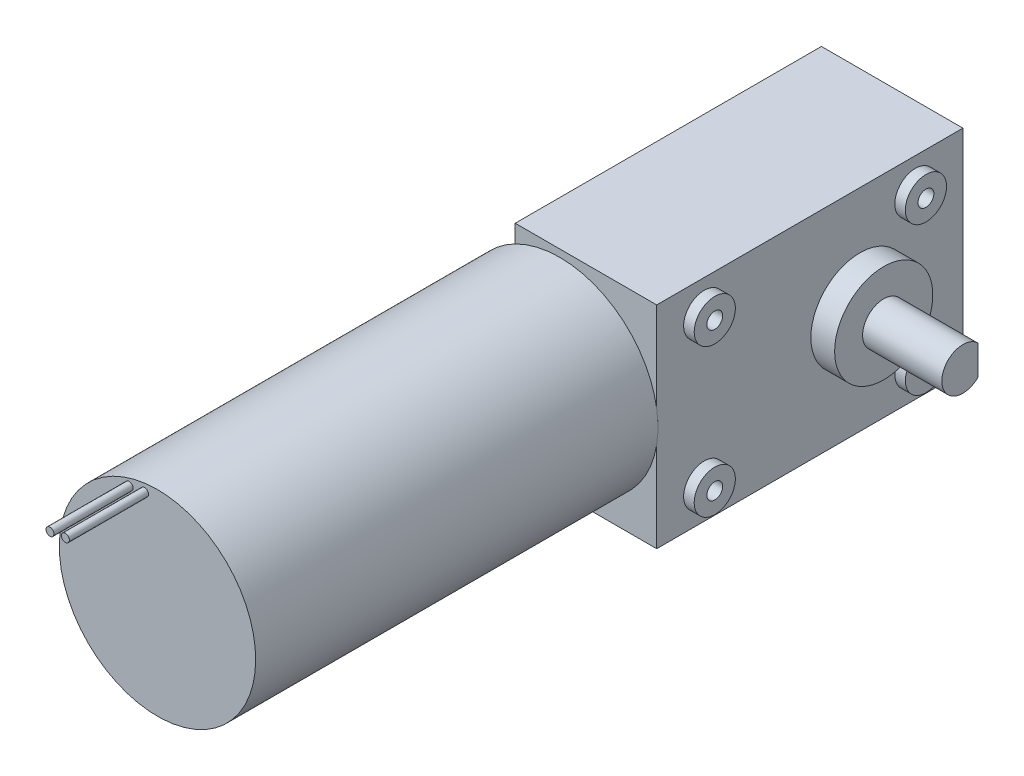
SolidWorks part; units mm, degrees
ref_plane "Front Plane" through (0, 0, 0) normal (0, 0, 1) x (1, 0, 0)
ref_plane "Top Plane" through (0, 0, 0) normal (0, 1, 0) x (1, 0, 0)
ref_plane "Right Plane" through (0, 0, 0) normal (1, 0, 0) x (0, 0, -1)
sketch "Sketch4" plane through (0, 0, 0) normal (0, 0, 1) x (1, 0, 0)
  circle A0 centre (-63.8569, 21.8657) radius 18.6
  dimension "D1" = 37.2
extrude "Boss-Extrude3" add sketch "Sketch4" along normal blind 76.2
sketch "Sketch5" plane through (0, 0, 76.2) normal (0, 0, 1) x (1, 0, 0)
  circle A0 centre (-66.3053, 38.8201) radius 0.75
  dimension "D1" = 1.5
extrude "Boss-Extrude4" add sketch "Sketch5" along normal blind 15
sketch "Sketch6" plane through (0, 0, 76.2) normal (0, 0, 1) x (1, 0, 0)
  circle A0 centre (-69.2249, 38.365) radius 0.75
  dimension "D1" = 1.5
extrude "Boss-Extrude5" add sketch "Sketch6" along normal blind 15
sketch "Sketch7" plane through (0, 0, 0) normal (0, 0, -1) x (-1, 0, 0)
  line L1 (72.2953, 41.836) -> (45.4953, 41.836)
  line L2 (72.2953, 41.836) -> (72.2953, 1.836)
  line L3 (72.2953, 1.836) -> (45.4953, 1.836)
  line L4 (45.4953, 41.836) -> (45.4953, 1.836)
  dimension "D1" = 26.8
  dimension "D2" = 40
extrude "Boss-Extrude6" add sketch "Sketch7" along normal blind 58
sketch "Sketch22" plane through (-72.2953, 0, 0) normal (-1, 0, 0) x (0, 0, 1)
  line L0 (-58, 41.836) -> (0, 41.836) construction
  line L1 (-49, 35.836) -> (-9, 35.836)
  line L2 (-49, 35.836) -> (-49, 7.836)
  line L3 (-49, 7.836) -> (-9, 7.836)
  line L4 (-9, 35.836) -> (-9, 7.836)
  line L5 (-49, 35.836) -> (-9, 7.836) construction
  line L6 (-49, 7.836) -> (-9, 35.836) construction
  line L7 (-58, 1.836) -> (-58, 41.836) construction
  line L8 (0, 38.4413) -> (0, 5.29) construction
  line L9 (-58, 21.836) -> (-29, 21.836)
  circle A0 centre (-49, 35.836) radius 1.5
  circle A1 centre (-49, 7.836) radius 1.5
  circle A2 centre (-9, 7.836) radius 1.5
  circle A3 centre (-9, 35.836) radius 1.5
  circle A4 centre (-38.5, 21.836) radius 9.3
  circle A5 centre (-49, 7.836) radius 3.9
  circle A6 centre (-49, 35.836) radius 3.9
  circle A7 centre (-9, 35.836) radius 3.9
  circle A8 centre (-9, 7.836) radius 3.9
  point P4 (-29, 21.836)
  dimension "D6" = 3
  dimension "D7" = 3
  dimension "D8" = 3
  dimension "D9" = 3
  dimension "D10" = 18.6
  dimension "D11" = 19.5
  dimension "D12" = 7.8
  dimension "D13" = 7.8
  dimension "D14" = 7.8
  dimension "D15" = 7.8
  dimension "D1" = 40
  dimension "D2" = 28
  dimension "D3" = 6
  dimension "D4" = 9
  dimension "D5" = 9
extrude "Boss-Extrude10" add sketch "Sketch22" along normal blind 1.8 contours L9 A4 | L9 A4 | L2 A5 L3 A1 | L3 A5 L2 A1 | L2 A6 L1 A0 | L1 A6 L2 A0 | L1 A7 L4 A3 | L4 A7 L1 A3 | L4 A8 L3 A2 | L3 A8 L4 A2 region at (-72.2953, 36.9746, -50.1387) region at (-72.2953, 34.0039, -47.1679) region at (-72.2953, 25.783, -38.5) region at (-72.2953, 17.8889, -38.5) region at (-72.2953, 39.6256, -9) region at (-72.2953, 34.0039, -10.8321) region at (-72.2953, 9.668, -47.1679) region at (-72.2953, 10.536, -49.1103) region at (-72.2953, 10.5157, -6.3203) region at (-72.2953, 9.668, -10.8321)
extrude "Boss-Extrude11" add sketch "Sketch22<4>" along normal blind 4.5 contours L9 A4 | L9 A4 region at (-72.2953, 25.783, -38.5) region at (-72.2953, 17.8889, -38.5)
sketch "Sketch22<4>" plane through (-72.2953, 0, 0) normal (-1, 0, 0) x (0, 0, 1) same geometry as "Sketch22"
extrude "Cut-Extrude1" cut sketch "Sketch22<5>" against normal blind 5.3 from surface contours L2 A1 L3 | L3 A1 L2 | L1 A0 L2 | L2 A0 L1 | L4 A3 L1 | L1 A3 L4 | L3 A2 L4 | L4 A2 L3 region at (-72.2953, 36.0482, -49.2122) region at (-72.2953, 35.1993, -48.3634) region at (-72.2953, 36.0482, -8.7878) region at (-72.2953, 35.1993, -9.6366) region at (-72.2953, 8.4726, -48.3634) region at (-72.2953, 7.6237, -49.2122) region at (-72.2953, 7.6237, -8.7878) region at (-72.2953, 8.4726, -9.6366) starting at face at (-74.0953, 7.836, -47.5)
sketch "Sketch22<5>" plane through (-72.2953, 0, 0) normal (-1, 0, 0) x (0, 0, 1) same geometry as "Sketch22"
extrude "Boss-Extrude12" add sketch "Sketch22<6>" against normal blind 2 from surface contours L4 A7 L1 A3 | L1 A7 L4 A3 | L3 A8 L4 A2 | L4 A8 L3 A2 | L1 A6 L2 A0 | L2 A6 L1 A0 | L2 A5 L3 A1 | L3 A5 L2 A1 region at (-72.2953, 36.9746, -50.1387) region at (-72.2953, 34.0039, -47.1679) region at (-72.2953, 39.6256, -9) region at (-72.2953, 34.0039, -10.8321) region at (-72.2953, 9.668, -47.1679) region at (-72.2953, 10.536, -49.1103) region at (-72.2953, 10.5157, -6.3203) region at (-72.2953, 9.668, -10.8321) starting at face at (-45.4953, 21.8459, -19.3333)
sketch "Sketch22<6>" plane through (-72.2953, 0, 0) normal (-1, 0, 0) x (0, 0, 1) same geometry as "Sketch22"
extrude "Cut-Extrude2" cut sketch "Sketch22<7>" along normal blind 5.3 from surface contours L3 A2 L4 | L4 A2 L3 | L4 A3 L1 | L1 A3 L4 | L1 A0 L2 | L2 A0 L1 | L2 A1 L3 | L3 A1 L2 region at (-72.2953, 36.0482, -49.2122) region at (-72.2953, 35.1993, -48.3634) region at (-72.2953, 36.0482, -8.7878) region at (-72.2953, 35.1993, -9.6366) region at (-72.2953, 8.4726, -48.3634) region at (-72.2953, 7.6237, -49.2122) region at (-72.2953, 7.6237, -8.7878) region at (-72.2953, 8.4726, -9.6366) starting at face at (-43.4953, 35.836, -7.5)
sketch "Sketch22<7>" plane through (-72.2953, 0, 0) normal (-1, 0, 0) x (0, 0, 1) same geometry as "Sketch22"
extrude "Boss-Extrude13" add sketch "Sketch22<8>" against normal blind 4.5 from surface contours L9 A4 | L9 A4 region at (-72.2953, 25.783, -38.5) region at (-72.2953, 17.8889, -38.5) starting at face at (-45.4953, 7.836, -45.1)
sketch "Sketch22<8>" plane through (-72.2953, 0, 0) normal (-1, 0, 0) x (0, 0, 1) same geometry as "Sketch22"
sketch "Sketch21" plane through (-40.9953, 0, 0) normal (1, 0, 0) x (0, 0, -1)
  line L1 (41.36, 24.6324) -> (41.36, 19.0395)
  circle A0 centre (38.5, 21.836) radius 4
  circle A2 centre (38.5, 21.836) radius 9.3 construction
  dimension "D1" = 8
  dimension "D2" = 2.86
extrude "Boss-Extrude14" add sketch "Sketch21" along normal blind 15 contours L1 A0 region at (-40.9953, 21.836, -38.1822)
